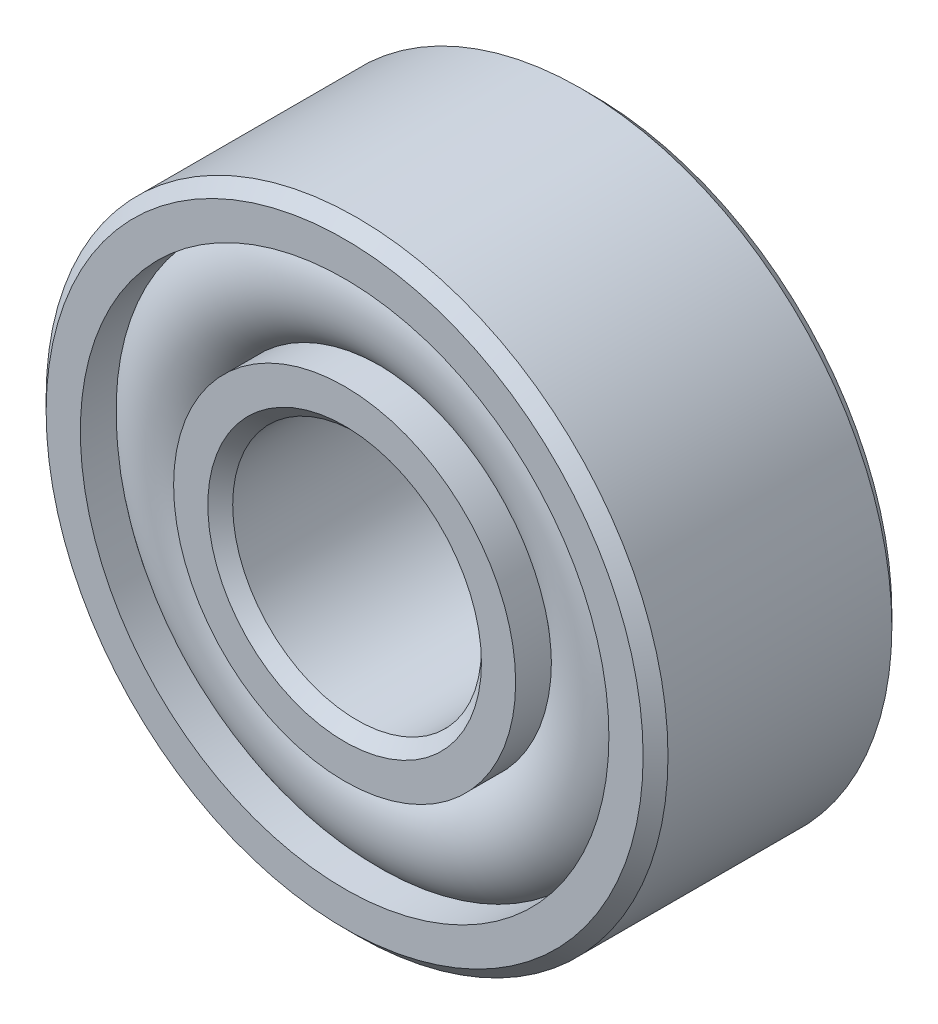
SolidWorks part; units mm, degrees
material "Stainless Steel (ferritic)"
ref_plane "Front Plane" through (0, 0, 0) normal (0, 0, 1) x (1, 0, 0)
ref_plane "Top Plane" through (0, 0, 0) normal (0, 1, 0) x (1, 0, 0)
ref_plane "Right Plane" through (0, 0, 0) normal (1, 0, 0) x (0, 0, -1)
sketch "Sketch1" plane through (0, 0, 0) normal (0, 1, 0) x (1, 0, 0)
  line L0 (2.75, 3.4248) -> (2.75, 4)
  line L1 (2.75, 4) -> (2, 4)
  line L2 (2, 4) -> (2, 0)
  line L3 (2, 0) -> (2.75, 0)
  line L4 (2.75, 0) -> (2.75, 0.5752)
  line L5 (4.25, 0.5752) -> (4.25, 0)
  line L6 (4.25, 0) -> (5, 0)
  line L7 (5, 0) -> (5, 4)
  line L8 (5, 4) -> (4.25, 4)
  line L9 (4.25, 4) -> (4.25, 3.4248)
  line L10 (0, 4) -> (0, 0) construction
  line L11 (0, 4) -> (2, 4) construction
  line L12 (2, 0) -> (0, 0) construction
  line L13 (3.5, 4) -> (3.5, 3.75) construction
  line L14 (0, 2) -> (5, 2) construction
  line L15 (2.75, 4) -> (4.25, 4) construction
  arc A0 (4.25, 0.5752) -> (2.75, 0.5752) centre (3.5, 1.2775) cw
  arc A1 (4.25, 3.4248) -> (2.75, 3.4248) centre (3.5, 2.7225) ccw
  dimension "D6" = 0.25
  dimension "D1" = 4
  dimension "D2" = 2
  dimension "D3" = 0.75
  dimension "D4" = 5
  dimension "D5" = 0.75
revolve "Revolve1" add sketch "Sketch1" angle 360 about L10 reverse direction yes
chamfer "Chamfer1" distance 0.2 angle 45 1 edges at (5, 0, -4)
chamfer "Chamfer2" distance 0.2 angle 45 1 edges at (2, 0, -4)
chamfer "Chamfer3" distance 0.2 angle 45 1 edges at (5, 0, 0)
chamfer "Chamfer4" distance 0.2 angle 45 1 edges at (2, 0, 0)
